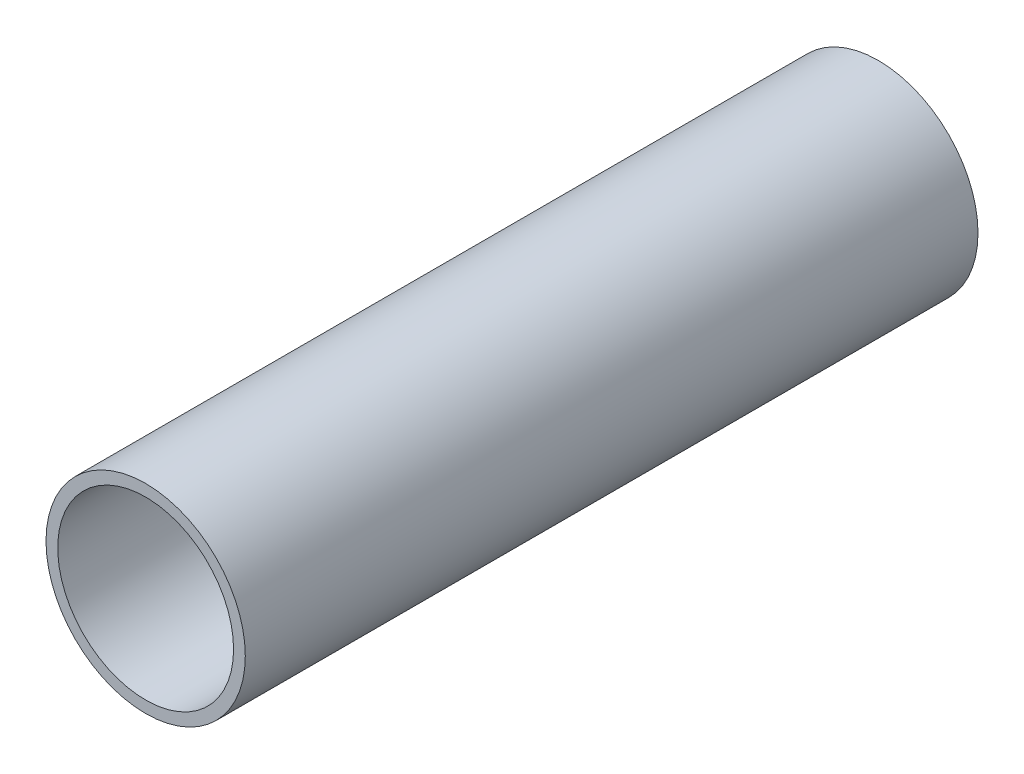
SolidWorks part; units mm, degrees
ref_plane "Front Plane" through (0, 0, 0) normal (0, 0, 1) x (1, 0, 0)
ref_plane "Top Plane" through (0, 0, 0) normal (0, 1, 0) x (1, 0, 0)
ref_plane "Right Plane" through (0, 0, 0) normal (1, 0, 0) x (0, 0, -1)
sketch "Sketch1" plane through (0, 0, 0) normal (0, 0, 1) x (1, 0, 0)
  circle A0 centre (0, 0) radius 30
  circle A1 centre (0, 0) radius 34
  dimension "D1" = 60
  dimension "D2" = 4
extrude "Boss-Extrude1" add sketch "Sketch1" along normal blind 250
